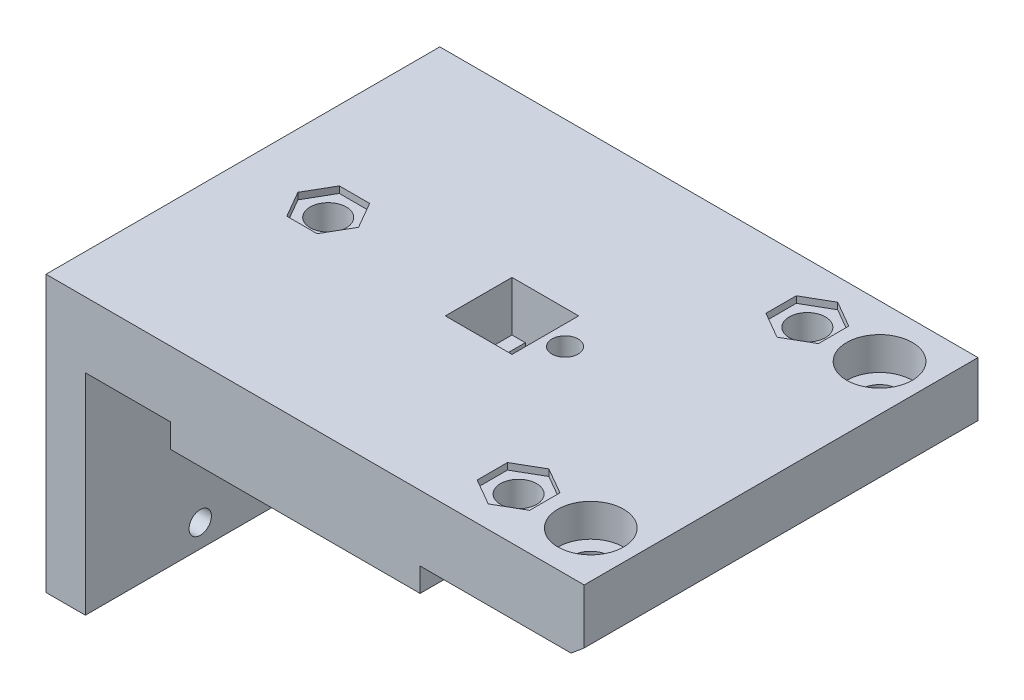
SolidWorks part; units mm, degrees
ref_plane "Front Plane" through (0, 0, 0) normal (0, 0, 1) x (1, 0, 0)
ref_plane "Top Plane" through (0, 0, 0) normal (0, 1, 0) x (1, 0, 0)
ref_plane "Right Plane" through (0, 0, 0) normal (1, 0, 0) x (0, 0, -1)
sketch "Sketch1" plane through (0, 0, 0) normal (0, 1, 0) x (1, 0, 0)
  line L1 (0, 0) -> (82, 0)
  line L2 (0, 0) -> (0, 60)
  line L3 (0, 60) -> (82, 60)
  line L4 (82, 0) -> (82, 60)
  dimension "D1" = 82
  dimension "D2" = 60
extrude "Boss-Extrude1" add sketch "Sketch1" along normal blind 10
sketch "Sketch2" plane through (0, 0, 0) normal (0, -1, 0) x (1, 0, 0)
  line L0 (0, 0) -> (82, 0) construction
  line L1 (0, -60) -> (6, -60)
  line L2 (0, -60) -> (0, 0)
  line L3 (0, 0) -> (6, 0)
  line L4 (6, -60) -> (6, 0)
  dimension "D1" = 6
extrude "Boss-Extrude2" add sketch "Sketch2" along normal blind 32
sketch "Sketch3" plane through (0, 0, 0) normal (-1, 0, 0) x (0, 0, 1)
  line L0 (0, -16) -> (-60, -16) construction
  line L1 (0, 10) -> (0, -32) construction
  line L2 (-60, 10) -> (-60, -32) construction
  line L5 (-60, -32) -> (-60, 0) construction
  line L6 (-17.5, -3.5) -> (-42.5, -3.5)
  line L7 (-17.5, -3.5) -> (-17.5, -28.5)
  line L8 (-17.5, -28.5) -> (-42.5, -28.5)
  line L9 (-42.5, -3.5) -> (-42.5, -28.5)
  line L10 (-17.5, -3.5) -> (-42.5, -28.5) construction
  line L11 (-17.5, -28.5) -> (-42.5, -3.5) construction
  point P7 (-30, -16)
  dimension "D1" = 25
hole_wizard "M3 Clearance Hole1" positions "Sketch4" profile "Sketch5" hole size "M3" standard "ANSI Metric" end condition through all
sketch "Sketch4" plane through (0, 0, 0) normal (-1, 0, 0) x (0, 0, 1)
  point P0 (-42.5, -28.5)
  point P3 (-42.5, -3.5)
  point P6 (-17.5, -3.5)
  point P9 (-17.5, -28.5)
sketch "Sketch5" plane through (0, -28.5, -42.5) normal (0, 1, 0) x (0, 0, 1)
  line L0 (0, 0) -> (0, 82)
  line L1 (0, 82) -> (1.7, 82)
  line L2 (1.7, 82) -> (1.7, 0)
  line L5 (1.7, 0) -> (0, 0)
  line L11 (0, -6.35) -> (0, 107.95) construction
  dimension "Thru Hole Dia." = 3.4
  dimension "Thru Hole Depth" = 82
ref_plane "Plane1" through (0, -16, 0) normal (0, -1, 0) x (-1, 0, 0)
ref_plane "Plane2" through (0, -4, 0) normal (0, -1, 0) x (-1, 0, 0)
ref_plane "Belt Plane" through (0, -3.624, 0) normal (0, -1, 0) x (-1, 0, 0)
sketch "Sketch7" plane through (0, 0, 0) normal (0, -1, 0) x (1, 0, 0)
  line L0 (82, -60) -> (6, -60) construction
  line L1 (19, -60) -> (57, -60)
  line L2 (19, -60) -> (19, 0)
  line L3 (19, 0) -> (57, 0)
  line L4 (57, -60) -> (57, 0)
  line L5 (6, 0) -> (82, 0) construction
  line L6 (6, -60) -> (6, 0) construction
  line L8 (82, 0) -> (82, -60) construction
  dimension "D1" = 13
  dimension "D2" = 25
extrude "Boss-Extrude3" add sketch "Sketch7" along normal up to surface (3.624 mm away) up to plane "Belt Plane"
sketch "Sketch8" plane through (0, -3.624, 0) normal (0, -1, 0) x (1, 0, 0)
  line L0 (41, -60) -> (41, 0) construction
  line L1 (19, -60) -> (57, -60) construction
  line L2 (57, 0) -> (19, 0) construction
  line L4 (6, -60) -> (6, 0) construction
  dimension "D1" = 35
hole_wizard "M4 Clearance Hole1" positions "Sketch9" profile "Sketch10" hole size "M4" standard "ANSI Metric" end condition through all
sketch "Sketch9" plane through (0, -3.624, 0) normal (0, -1, 0) x (-1, 0, 0)
  line L0 (-41, 60) -> (-41, 0) construction
  point P0 (-41, 30)
sketch "Sketch10" plane through (41, -3.624, -30) normal (1, 0, 0) x (0, 0, -1)
  line L0 (0, 0) -> (0, 13.624)
  line L1 (0, 13.624) -> (2.25, 13.624)
  line L2 (2.25, 13.624) -> (2.25, 0)
  line L5 (2.25, 0) -> (0, 0)
  line L11 (0, -6.35) -> (0, 107.95) construction
  dimension "Thru Hole Dia." = 4.5
  dimension "Thru Hole Depth" = 13.624
sketch "Sketch11" plane through (0, 10, 0) normal (0, 1, 0) x (1, 0, 0)
  line L1 (35.92, 24.92) -> (46.08, 24.92)
  line L2 (35.92, 24.92) -> (35.92, 35.08)
  line L3 (35.92, 35.08) -> (46.08, 35.08)
  line L4 (46.08, 24.92) -> (46.08, 35.08)
  line L5 (35.92, 24.92) -> (46.08, 35.08) construction
  line L6 (35.92, 35.08) -> (46.08, 24.92) construction
  point P0 (41, 30)
  dimension "D1" = 10.16
extrude "Cut-Extrude1" cut sketch "Sketch11" against normal offset from surface (9.124 mm away) 4.5 up to face at (41, -3.624, -32.25)
sketch "Sketch12" plane through (0, 0.876, 0) normal (0, 1, 0) x (1, 0, 0)
  line L0 (46.08, 35.08) -> (35.92, 35.08) construction
  line L1 (35.92, 24.92) -> (37.952, 24.92)
  line L2 (35.92, 24.92) -> (35.92, 35.08)
  line L3 (35.92, 35.08) -> (37.952, 35.08)
  line L4 (37.952, 24.92) -> (37.952, 35.08)
  line L6 (46.08, 24.92) -> (44.048, 24.92)
  line L7 (46.08, 24.92) -> (46.08, 35.08)
  line L8 (46.08, 35.08) -> (44.048, 35.08)
  line L9 (44.048, 24.92) -> (44.048, 35.08)
  dimension "D1" = 6.096
extrude "Boss-Extrude4" add sketch "Sketch12" along normal blind 1.524
ref_plane "Plane4" through (41, 0, 0) normal (-1, 0, 0) x (0, 0, 1)
sketch "Sketch15" plane through (0, 10, 0) normal (0, 1, 0) x (1, 0, 0)
  line L0 (75, 60) -> (75, 0) construction
  line L1 (82, 60) -> (0, 60) construction
  line L2 (0, 0) -> (82, 0) construction
  line L3 (82, 0) -> (82, 60) construction
  point P8 (75, 52)
  point P9 (75, 8)
  dimension "D1" = 7
  dimension "D2" = 8
  dimension "D3" = 8
hole_wizard "CBORE for M5 SHCS2" positions "Sketch18" profile "Sketch19" counterbore size "M5" standard "ANSI Metric" end condition through all
sketch "Sketch18" plane through (0, 10, 0) normal (0, 1, 0) x (1, 0, 0)
  point P0 (75, 52)
  point P3 (75, 8)
sketch "Sketch19" plane through (75, 10, -52) normal (1, 0, 0) x (0, 0, 1)
  line L0 (0, 0) -> (0, 42)
  line L1 (0, 42) -> (2.75, 42)
  line L3 (2.75, 42) -> (2.75, 5)
  line L4 (2.75, 5) -> (5, 5)
  line L5 (5, 5) -> (5, 0)
  line L7 (5, 0) -> (0, 0)
  line L11 (0, -6.35) -> (0, 107.95) construction
  dimension "Thru Hole Dia." = 5.5
  dimension "Thru Hole Depth" = 42
  dimension "C'Bore Dia." = 10
  dimension "C'Bore Depth" = 5
chamfer "Chamfer1" distance 2 angle 40 1 edges at (82, 0, -30) first distance on face at (75, 0, -54.75)
sketch "Sketch20" plane through (0, 10, 0) normal (0, 1, 0) x (1, 0, 0)
  line L0 (64, 0) -> (64, 60) construction
  line L1 (0, 0) -> (82, 0) construction
  line L2 (82, 60) -> (0, 60) construction
  line L3 (64, 60) -> (13, 30) construction
  line L5 (13, 30) -> (64, 0) construction
  line L6 (13, 30) -> (0, 30) construction
  line L7 (0, 60) -> (0, 0) construction
  line L8 (64, 12.6188) -> (60, 10.3094)
  line L9 (60, 10.3094) -> (60, 5.6906)
  line L10 (60, 5.6906) -> (64, 3.3812)
  line L11 (64, 3.3812) -> (68, 5.6906)
  line L12 (68, 5.6906) -> (68, 10.3094)
  line L13 (68, 10.3094) -> (64, 12.6188)
  line L14 (64, 47.3812) -> (68, 49.6906)
  line L15 (68, 49.6906) -> (68, 54.3094)
  line L16 (68, 54.3094) -> (64, 56.6188)
  line L17 (64, 56.6188) -> (60, 54.3094)
  line L18 (60, 54.3094) -> (60, 49.6906)
  line L19 (60, 49.6906) -> (64, 47.3812)
  line L20 (10.6906, 26) -> (15.3094, 26)
  line L21 (15.3094, 26) -> (17.6188, 30)
  line L22 (17.6188, 30) -> (15.3094, 34)
  line L23 (15.3094, 34) -> (10.6906, 34)
  line L24 (10.6906, 34) -> (8.3812, 30)
  line L25 (8.3812, 30) -> (10.6906, 26)
  line L26 (82, 0) -> (82, 60) construction
  circle A0 centre (64, 8) radius 4 construction
  circle A1 centre (64, 52) radius 4 construction
  circle A2 centre (13, 30) radius 4 construction
  dimension "D1" = 13
  dimension "D2" = 8
  dimension "D3" = 8
  dimension "D4" = 8
  dimension "D5" = 18
extrude "Cut-Extrude2" cut sketch "Sketch20" against normal blind 1
sketch "Sketch21" plane through (0, 0, 0) normal (0, -1, 0) x (1, 0, 0)
  line L0 (68, -10.3094) -> (64, -12.6188) construction
  line L1 (64, -12.6188) -> (60, -10.3094) construction
  line L2 (60, -10.3094) -> (60, -5.6906) construction
  line L3 (60, -5.6906) -> (64, -3.3812) construction
  line L4 (64, -3.3812) -> (68, -5.6906) construction
  line L5 (68, -5.6906) -> (68, -10.3094) construction
  line L6 (60, -49.6906) -> (64, -47.3812) construction
  line L7 (64, -47.3812) -> (68, -49.6906) construction
  line L8 (68, -49.6906) -> (68, -54.3094) construction
  line L9 (68, -54.3094) -> (64, -56.6188) construction
  line L10 (64, -56.6188) -> (60, -54.3094) construction
  line L11 (60, -54.3094) -> (60, -49.6906) construction
  line L12 (68, -10.3094) -> (64, -12.6188)
  line L13 (64, -12.6188) -> (60, -10.3094)
  line L14 (60, -10.3094) -> (60, -5.6906)
  line L15 (60, -5.6906) -> (64, -3.3812)
  line L16 (64, -3.3812) -> (68, -5.6906)
  line L17 (68, -5.6906) -> (68, -10.3094)
  line L18 (60, -49.6906) -> (64, -47.3812)
  line L19 (64, -47.3812) -> (68, -49.6906)
  line L20 (68, -49.6906) -> (68, -54.3094)
  line L21 (68, -54.3094) -> (64, -56.6188)
  line L22 (64, -56.6188) -> (60, -54.3094)
  line L23 (60, -54.3094) -> (60, -49.6906)
  line L24 (64, -56.6188) -> (64, -47.3812)
  line L25 (64, -12.6188) -> (64, -3.3812)
  line L26 (10.6906, -34) -> (15.3094, -26)
  line L32 (10.6906, -26) -> (8.3812, -30)
  line L33 (15.3094, -26) -> (10.6906, -26)
  line L34 (17.6188, -30) -> (15.3094, -26)
  line L35 (15.3094, -34) -> (17.6188, -30)
  line L36 (10.6906, -34) -> (15.3094, -34)
  line L37 (8.3812, -30) -> (10.6906, -34)
  line L38 (10.6906, -26) -> (8.3812, -30)
  line L39 (15.3094, -26) -> (10.6906, -26)
  line L40 (17.6188, -30) -> (15.3094, -26)
  line L41 (15.3094, -34) -> (17.6188, -30)
  line L42 (10.6906, -34) -> (15.3094, -34)
  line L43 (8.3812, -30) -> (10.6906, -34)
  dimension "D1" = 0
hole_wizard "CBORE for M5 SHCS3" positions "Sketch22" profile "Sketch23" counterbore size "M5" standard "ANSI Metric" end condition through all
sketch "Sketch22" plane through (0, 0, 0) normal (0, -1, 0) x (-1, 0, 0)
  line L0 (-64, 12.6188) -> (-64, 3.3812) construction
  line L1 (-64, 56.6188) -> (-64, 47.3812) construction
  line L2 (-10.6906, 34) -> (-15.3094, 26) construction
  point P0 (-64, 52)
  point P2 (-64, 8)
  point P11 (-13, 30)
sketch "Sketch23" plane through (64, 0, -52) normal (1, 0, 0) x (0, 0, -1)
  line L0 (0, 0) -> (0, 10)
  line L1 (0, 10) -> (2.75, 10)
  line L3 (2.75, 10) -> (2.75, 5)
  line L4 (2.75, 5) -> (5, 5)
  line L5 (5, 5) -> (5, 0)
  line L7 (5, 0) -> (0, 0)
  line L11 (0, -6.35) -> (0, 107.95) construction
  dimension "Thru Hole Dia." = 5.5
  dimension "Thru Hole Depth" = 10
  dimension "C'Bore Dia." = 10
  dimension "C'Bore Depth" = 5
sketch "Sketch24" plane through (0, 10, 0) normal (0, 1, 0) x (1, 0, 0)
  line L0 (46.08, 30) -> (49.08, 30) construction
  line L1 (46.08, 24.92) -> (46.08, 35.08) construction
  circle A0 centre (49.08, 30) radius 16
  circle A1 centre (49.08, 30) radius 2.5
  circle A2 centre (49.08, 30) radius 2
  dimension "D1" = 32
  dimension "D2" = 5
  dimension "D3" = 4
  dimension "D4" = 3
extrude "Cut-Extrude3" cut sketch "Sketch24" against normal through all and the other way through all contours A2 region at (49.08, 10, -30)
